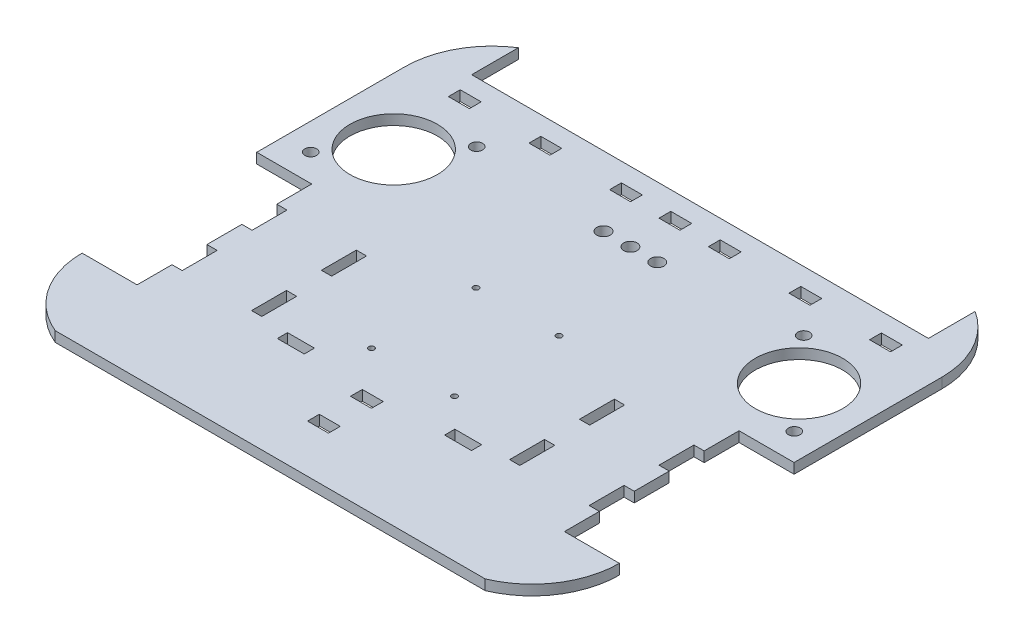
SolidWorks part; units mm, degrees
ref_plane "Front Plane" through (0, 0, 0) normal (0, 0, 1) x (1, 0, 0)
ref_plane "Top Plane" through (0, 0, 0) normal (0, 1, 0) x (1, 0, 0)
ref_plane "Right Plane" through (0, 0, 0) normal (1, 0, 0) x (0, 0, -1)
sketch "Sketch1" plane through (0, 0, 0) normal (0, 1, 0) x (1, 0, 0)
  line L1 (-127, 114.3) -> (127, 114.3)
  line L2 (-127, 114.3) -> (-127, -114.3)
  line L3 (-127, -114.3) -> (127, -114.3)
  line L4 (127, 114.3) -> (127, -114.3)
  line L5 (-127, 114.3) -> (127, -114.3) construction
  line L6 (-127, -114.3) -> (127, 114.3) construction
  point P0 (0, 0)
  dimension "D1" = 254
  dimension "D2" = 228.6
extrude "Boss-Extrude1" add sketch "Sketch1" along normal blind 4.826
sketch "Sketch2" plane through (0, 4.826, 0) normal (0, 1, 0) x (1, 0, 0)
  line L0 (-127, 114.3) -> (-127, -114.3) construction
  line L1 (-127, 6.35) -> (-101, 6.35)
  line L2 (-127, 6.35) -> (-127, -76.2)
  line L3 (-127, -76.2) -> (-101, -76.2)
  line L4 (-101, 6.35) -> (-101, -76.2)
  line L5 (127, -114.3) -> (127, 114.3) construction
  line L6 (127, 6.35) -> (101, 6.35)
  line L7 (127, 6.35) -> (127, -76.2)
  line L8 (127, -76.2) -> (101, -76.2)
  line L9 (101, 6.35) -> (101, -76.2)
  line L10 (-127, -114.3) -> (127, -114.3) construction
  dimension "D1" = 38.1
  dimension "D2" = 38.1
  dimension "D3" = 82.55
  dimension "D4" = 82.55
  dimension "D5" = 26
  dimension "D6" = 26
extrude "Cut-Extrude1" cut sketch "Sketch2" against normal blind 4.826
sketch "Sketch4" plane through (0, 4.826, 0) normal (0, 1, 0) x (1, 0, 0)
  line L0 (0, -114.3) -> (0, 114.3) construction
  line L1 (-127, -114.3) -> (127, -114.3) construction
  line L2 (127, 114.3) -> (-127, 114.3) construction
  line L3 (-127, 76.2) -> (-101.6, 76.2) construction
  line L4 (-127, 114.3) -> (-127, 6.35) construction
  line L5 (-101.6, 76.2) -> (-101.6, 114.3) construction
  line L6 (-127, 76.2) -> (-127, 114.3)
  line L7 (-127, 114.3) -> (-101.6, 114.3)
  line L8 (127, 76.2) -> (127, 114.3)
  line L9 (127, 114.3) -> (101.6, 114.3)
  arc A0 (-127, 76.2) -> (-101.6, 114.3) centre (-85.725, 76.2) cw
  arc A1 (127, 76.2) -> (101.6, 114.3) centre (85.725, 76.2) ccw
  dimension "D2" = 38.1
extrude "Cut-Extrude3" cut sketch "Sketch4" against normal blind 4.826
sketch "Sketch7" plane through (0, 4.826, 0) normal (0, 1, 0) x (1, 0, 0)
  line L0 (0, -114.3) -> (0, 114.3) construction
  line L1 (-127, -114.3) -> (127, -114.3) construction
  line L2 (101.6, 114.3) -> (-101.6, 114.3) construction
  line L3 (107.95, 88.9) -> (107.95, 114.3)
  line L4 (107.95, 88.9) -> (-107.95, 88.9)
  line L5 (0, 88.9) -> (0, 114.3)
  line L6 (107.95, 114.3) -> (-107.95, 114.3)
  line L7 (-107.95, 88.9) -> (-107.95, 114.3)
  line M6 (101.6, 114.3) -> (-101.6, 114.3)
  dimension "D2" = 107.95
extrude "Cut-Extrude5" cut sketch "Sketch7" against normal blind 4.826 contours L7 L4 L5 M6 | L5 L4 L3 M6 region at (53.975, 4.826, -101.6) region at (-53.975, 4.826, -101.6)
sketch "Sketch8" plane through (0, 4.826, 0) normal (0, 1, 0) x (1, 0, 0)
  line L0 (-127, -76.2) -> (-101.6, -76.2) construction
  line L1 (-101.6, -76.2) -> (-101.6, -114.3) construction
  line L2 (-127, -114.3) -> (127, -114.3) construction
  line L3 (-127, -76.2) -> (-127, -114.3)
  line L4 (-127, -114.3) -> (-101.6, -114.3)
  line L5 (0, -114.3) -> (0, 88.9) construction
  line L6 (107.95, 88.9) -> (-107.95, 88.9) construction
  line L7 (127, -114.3) -> (101.6, -114.3)
  line L8 (127, -76.2) -> (127, -114.3)
  arc A0 (-127, -76.2) -> (-101.6, -114.3) centre (-85.725, -76.2) ccw
  arc A1 (127, -76.2) -> (101.6, -114.3) centre (85.725, -76.2) cw
extrude "Cut-Extrude6" cut sketch "Sketch8" against normal blind 4.826
sketch "Sketch10" plane through (0, 4.826, 0) normal (0, 1, 0) x (1, 0, 0)
  line L0 (-101, -76.2) -> (-101, 6.35) construction
  line L1 (-101, -10.16) -> (-96.174, -10.16)
  line L2 (-101, -10.16) -> (-101, -26.67)
  line L3 (-101, -26.67) -> (-96.174, -26.67)
  line L4 (-96.174, -10.16) -> (-96.174, -26.67)
  line L5 (101, 6.35) -> (101, -76.2) construction
  line L6 (-101, -43.18) -> (-96.174, -43.18)
  line L7 (-101, -43.18) -> (-101, -59.69)
  line L8 (-101, -59.69) -> (-96.174, -59.69)
  line L9 (-96.174, -43.18) -> (-96.174, -59.69)
  line L10 (101, -10.16) -> (96.174, -10.16)
  line L11 (101, -10.16) -> (101, -26.67)
  line L12 (101, -26.67) -> (96.174, -26.67)
  line L13 (96.174, -10.16) -> (96.174, -26.67)
  line L14 (-101, 6.35) -> (-96.174, 6.35) construction
  line L15 (101, -43.18) -> (96.174, -43.18)
  line L16 (101, -43.18) -> (101, -59.69)
  line L17 (101, -59.69) -> (96.174, -59.69)
  line L18 (96.174, -43.18) -> (96.174, -59.69)
  line L19 (-96.174, 6.35) -> (-96.174, -10.16) construction
  line L20 (-96.174, -26.67) -> (-96.174, -43.18) construction
  line L21 (-96.174, -43.18) -> (-83.474, -80.9089) construction
  line L22 (-101, -76.2) -> (-96.174, -76.2)
  line L23 (-96.174, -76.2) -> (-96.174, -59.69)
  line L24 (-96.174, -59.69) -> (-83.474, -98.2941)
  line L25 (101, -76.2) -> (96.174, -76.2)
  line L26 (96.174, -76.2) -> (96.174, -59.69)
  line L27 (96.174, -43.18) -> (96.174, -26.67)
  line L28 (101, 6.35) -> (96.174, 6.35)
  line L29 (96.174, 6.35) -> (96.174, -10.16)
  line M19 (101, -76.2) -> (101, 6.35)
  line M35 (-101, 6.35) -> (-101, -76.2)
  dimension "D1" = 4.826
  dimension "D2" = 4.826
extrude "Cut-Extrude8" cut sketch "Sketch10" against normal through all contours L9 L6 L8 M35 | L10 L13 L12 M19 | L15 L18 L17 M19 | L2 L3 L4 L1 region at (-98.587, 4.826, 51.435) region at (98.587, 4.826, 18.415) region at (98.587, 4.826, 51.435)
sketch "Sketch12" plane through (0, 0, 0) normal (0, -1, 0) x (1, 0, 0)
  line L0 (-58.582, 43.18) -> (-58.582, 59.69) construction
  line L1 (-58.582, 43.18) -> (-63.408, 43.18) construction
  line L2 (-63.408, 43.18) -> (-63.408, 59.69) construction
  line L3 (-58.582, 59.69) -> (-63.408, 59.69) construction
  line L4 (-58.582, 26.67) -> (-63.408, 26.67) construction
  line L5 (-58.582, 10.16) -> (-58.582, 26.67) construction
  line L6 (-58.582, 10.16) -> (-63.408, 10.16) construction
  line L7 (-63.408, 10.16) -> (-63.408, 26.67) construction
  line L8 (-58.582, 43.18) -> (-58.582, 59.69)
  line L9 (-58.582, 43.18) -> (-63.408, 43.18)
  line L10 (-63.408, 43.18) -> (-63.408, 59.69)
  line L11 (-58.582, 59.69) -> (-63.408, 59.69)
  line L12 (-58.582, 26.67) -> (-63.408, 26.67)
  line L13 (-58.582, 10.16) -> (-58.582, 26.67)
  line L14 (-58.582, 10.16) -> (-63.408, 10.16)
  line L15 (-63.408, 10.16) -> (-63.408, 26.67)
extrude "Cut-Extrude9" cut sketch "Sketch12" against normal through all
sketch "Sketch13" plane through (0, 4.826, 0) normal (0, 1, 0) x (1, 0, 0)
  line L0 (63.408, -43.18) -> (63.408, -59.69) construction
  line L1 (63.408, -43.18) -> (58.582, -43.18) construction
  line L2 (58.582, -43.18) -> (58.582, -59.69) construction
  line L3 (63.408, -59.69) -> (58.582, -59.69) construction
  line L4 (63.408, -26.67) -> (58.582, -26.67) construction
  line L5 (63.408, -10.16) -> (63.408, -26.67) construction
  line L6 (63.408, -10.16) -> (58.582, -10.16) construction
  line L7 (58.582, -10.16) -> (58.582, -26.67) construction
  line L8 (63.408, -43.18) -> (63.408, -59.69)
  line L9 (63.408, -43.18) -> (58.582, -43.18)
  line L10 (58.582, -43.18) -> (58.582, -59.69)
  line L11 (63.408, -59.69) -> (58.582, -59.69)
  line L12 (63.408, -26.67) -> (58.582, -26.67)
  line L13 (63.408, -10.16) -> (63.408, -26.67)
  line L14 (63.408, -10.16) -> (58.582, -10.16)
  line L15 (58.582, -10.16) -> (58.582, -26.67)
extrude "Cut-Extrude10" cut sketch "Sketch13" against normal through all
sketch "Sketch14" plane through (0, 4.826, 0) normal (0, 1, 0) x (1, 0, 0)
  line L0 (-127, 6.35) -> (127, 6.35) construction
  line L1 (0, 6.35) -> (0, -114.3) construction
  line L2 (-101.6, -114.3) -> (101.6, -114.3) construction
  line L3 (-22.86, 6.35) -> (-22.86, -114.3) construction
  line L4 (22.86, 6.35) -> (22.86, -114.3) construction
  dimension "D1" = 22.86
sketch "Sketch15" plane through (0, 4.826, 0) normal (0, 1, 0) x (1, 0, 0)
  circle A0 centre (19.5961, 2.6692) radius 1.3462 construction
  circle A1 centre (-19.6723, 2.6692) radius 1.3462 construction
  circle A2 centre (-19.6723, -46.7636) radius 1.3462 construction
  circle A3 centre (19.5961, -46.7636) radius 1.3462 construction
  circle A4 centre (19.5961, 2.6692) radius 1.3462
  circle A5 centre (-19.6723, 2.6692) radius 1.3462
  circle A6 centre (-19.6723, -46.7636) radius 1.3462
  circle A7 centre (19.5961, -46.7636) radius 1.3462
extrude "Cut-Extrude11" cut sketch "Sketch15" against normal through all
sketch "Sketch16" plane through (0, 4.826, 0) normal (0, 1, 0) x (1, 0, 0)
  line L0 (0, 88.9) -> (0, -114.3) construction
  line L1 (107.95, 88.9) -> (-107.95, 88.9) construction
  circle A0 centre (77.2939, 60.6102) radius 2.7781 construction
  circle A1 centre (114.3, 19.1646) radius 2.7781 construction
  circle A2 centre (95.7969, 39.8874) radius 20.6375 construction
  circle A3 centre (77.2939, 60.6102) radius 2.7781
  circle A4 centre (114.3, 19.1646) radius 2.7781
  circle A5 centre (95.7969, 39.8874) radius 20.6375
  circle A6 centre (-95.7969, 39.8874) radius 20.6375
  circle A7 centre (-77.2939, 60.6102) radius 2.7781
  circle A8 centre (-114.3, 19.1646) radius 2.7781
extrude "Cut-Extrude12" cut sketch "Sketch16" against normal through all
sketch "Sketch17" plane through (0, 4.826, 0) normal (0, 1, 0) x (1, 0, 0)
  line L0 (-56.4929, 80.0388) -> (-56.4929, 74.4508)
  line L1 (-104.4989, 80.0388) -> (-94.5929, 80.0388)
  line L2 (-104.4989, 80.0388) -> (-104.4989, 74.4508)
  line L3 (-104.4989, 74.4508) -> (-94.5929, 74.4508)
  line L4 (-94.5929, 80.0388) -> (-94.5929, 74.4508)
  line L9 (-66.3989, 80.0388) -> (-56.4929, 80.0388)
  line L10 (-66.3989, 80.0388) -> (-66.3989, 74.4508)
  line L11 (-66.3989, 74.4508) -> (-56.4929, 74.4508)
  line L12 (-18.3929, 80.0388) -> (-18.3929, 74.4508)
  line L13 (-28.2989, 80.0388) -> (-18.3929, 80.0388)
  line L14 (-28.2989, 80.0388) -> (-28.2989, 74.4508)
  line L15 (-28.2989, 74.4508) -> (-18.3929, 74.4508)
  line L16 (-127, 76.2) -> (-127, 6.35) construction
  line L17 (0, 88.9) -> (0, -114.3)
  line L18 (107.95, 88.9) -> (-107.95, 88.9) construction
  line L19 (-94.5929, 74.4508) -> (-78.3377, 74.4508) construction
  line L20 (18.3929, 80.0388) -> (18.3929, 74.4508)
  line L21 (28.2989, 80.0388) -> (18.3929, 80.0388)
  line L22 (28.2989, 80.0388) -> (28.2989, 74.4508)
  line L23 (28.2989, 74.4508) -> (18.3929, 74.4508)
  line L24 (56.4929, 80.0388) -> (56.4929, 74.4508)
  line L25 (66.3989, 74.4508) -> (56.4929, 74.4508)
  line L26 (66.3989, 80.0388) -> (66.3989, 74.4508)
  line L27 (66.3989, 80.0388) -> (56.4929, 80.0388)
  line L28 (104.4989, 80.0388) -> (94.5929, 80.0388)
  line L29 (104.4989, 80.0388) -> (104.4989, 74.4508)
  line L30 (104.4989, 74.4508) -> (94.5929, 74.4508)
  line L31 (94.5929, 80.0388) -> (94.5929, 74.4508)
  line L36 (4.953, 74.4508) -> (4.953, 80.0388)
  line L37 (4.953, 74.4508) -> (-4.953, 74.4508)
  line L38 (4.953, 80.0388) -> (-4.953, 80.0388)
  line L39 (-4.953, 74.4508) -> (-4.953, 80.0388)
  line L40 (4.953, 74.4508) -> (-4.953, 80.0388) construction
  line L41 (4.953, 80.0388) -> (-4.953, 74.4508) construction
  point P42 (0, 77.2448)
  dimension "D1" = 9.906
  dimension "D2" = 5.588
  dimension "D6" = 3
  dimension "D7" = 22.5011
  dimension "D8" = 9.906
  dimension "D9" = 0
extrude "Cut-Extrude13" cut sketch "Sketch17" against normal through all contours L28 L31 L30 L29 | L26 L27 L24 L25 | L23 L22 L21 L20 | L36 L38 L17 L37 | L39 L37 L17 L38 | L14 L15 L12 L13 | L10 L11 L0 L9 | L4 L1 L2 L3 region at (-61.4459, 4.826, -77.2448) region at (-99.5459, 4.826, -77.2448) region at (-23.3459, 4.826, -77.2448) region at (2.4765, 4.826, -77.2448) region at (-2.4765, 4.826, -77.2448) region at (23.3459, 4.826, -77.2448) region at (61.4459, 4.826, -77.2448) region at (99.5459, 4.826, -77.2448)
sketch "Sketch18" plane through (0, 4.826, 0) normal (0, 1, 0) x (1, 0, 0)
  line L0 (-4.953, -91.694) -> (4.953, -91.694)
  line L1 (-4.953, -91.694) -> (-4.953, -86.106)
  line L2 (4.953, -91.694) -> (4.953, -86.106)
  line L3 (-4.953, -86.106) -> (4.953, -86.106)
  line L4 (-4.953, -91.694) -> (4.953, -86.106) construction
  line L5 (4.953, -91.694) -> (-4.953, -86.106) construction
  line L6 (0, 6.35) -> (0, -114.3) construction
  line L7 (-4.953, -71.374) -> (4.953, -71.374)
  line L8 (-4.953, -71.374) -> (-4.953, -65.786)
  line L9 (4.953, -71.374) -> (4.953, -65.786)
  line L10 (-4.953, -65.786) -> (4.953, -65.786)
  line L11 (-4.953, -71.374) -> (4.953, -65.786) construction
  line L12 (4.953, -71.374) -> (-4.953, -65.786) construction
  point P1 (0, -88.9)
  point P10 (0, -68.58)
  dimension "D1" = 9.906
  dimension "D2" = 5.588
  dimension "D3" = 0
  dimension "D4" = 25.4
  dimension "D5" = 2
extrude "Cut-Extrude14" cut sketch "Sketch18" against normal through all
sketch "Sketch19" plane through (0, 4.826, 0) normal (0, 1, 0) x (1, 0, 0)
  circle A0 centre (0, 55.982) radius 3.175
  circle A1 centre (12.7, 55.982) radius 3.175
  circle A2 centre (-12.7, 55.982) radius 3.175
  dimension "D1" = 6.35
  dimension "D2" = 2
  dimension "D3" = 2
extrude "Cut-Extrude15" cut sketch "Sketch19" against normal through all
sketch "Sketch22" plane through (0, 0, 0) normal (0, -1, 0) x (1, 0, 0)
  line L0 (-33.182, 60.198) -> (-45.882, 60.198) construction
  line L1 (-33.182, 60.198) -> (-33.182, 65.024) construction
  line L2 (-33.182, 65.024) -> (-45.882, 65.024) construction
  line L3 (-45.882, 60.198) -> (-45.882, 65.024) construction
  line L4 (33.182, 60.198) -> (45.882, 60.198) construction
  line L5 (45.882, 65.024) -> (45.882, 60.198) construction
  line L6 (33.182, 65.024) -> (45.882, 65.024) construction
  line L7 (33.182, 65.024) -> (33.182, 60.198) construction
  line L8 (-33.182, 60.198) -> (-45.882, 60.198)
  line L9 (-33.182, 60.198) -> (-33.182, 65.024)
  line L10 (-33.182, 65.024) -> (-45.882, 65.024)
  line L11 (-45.882, 60.198) -> (-45.882, 65.024)
  line L12 (33.182, 60.198) -> (45.882, 60.198)
  line L13 (45.882, 65.024) -> (45.882, 60.198)
  line L14 (33.182, 65.024) -> (45.882, 65.024)
  line L15 (33.182, 65.024) -> (33.182, 60.198)
extrude "Cut-Extrude18" cut sketch "Sketch22" against normal through all
equation "\"MDF\"= 0.19in"
equation "\"GenDiameter\"= 60mm"
equation "\"GenCutDiameter\" = 1.8in"
equation "\"GenCutDistance\" = 1"
equation "\"TowerHeight\" = 6in"
equation "\"TowerFrontBase\" = 3in"
equation "\"FunnelHeight\" = 1in"
equation "\"FunnelAngle\" = 20"
equation "\"TowerSideBase\" = 3in"
equation "\"BaseLength\" = 9in"
equation "\"BaseWidth\" = 10in"
equation "\"WheelHoleLength\" = 3.25in"
equation "\"WheelHoleWidth\" = 26mm"
equation "\"DropLength\" = 1in"
equation "\"D1@Sketch1\"=\"BaseWidth\""
equation "\"D2@Sketch1\"=\"BaseLength\""
equation "\"D1@Boss-Extrude1\"=\"MDF\""
equation "\"WheelHoleFromBack\" = 1.5in"
equation "\"D1@Sketch2\"=\"WheelHoleFromBack\""
equation "\"D2@Sketch2\"=\"WheelHoleFromBack\""
equation "\"D3@Sketch2\"=\"WheelHoleLength\""
equation "\"D4@Sketch2\"=\"WheelHoleLength\""
equation "\"D5@Sketch2\"=\"WheelHoleWidth\""
equation "\"D6@Sketch2\"=\"WheelHoleWidth\""
equation "\"D1@Cut-Extrude1\"=\"MDF\""
equation "\"DropWidth\" = 8.5in"
equation "\"BumperWidth\" = 1in"
equation "\"D1@Sketch4\"=\"BumperWidth\""
equation "\"D2@Sketch4\"=\"WheelHoleFromBack\""
equation "\"D1@Cut-Extrude3\"=\"MDF\""
equation "\"D1@Sketch7\"=\"DropLength\""
equation "\"D2@Sketch7\"=\"DropWidth\"/2"
equation "\"D1@Cut-Extrude5\"=\"MDF\""
equation "\"D1@Sketch8\"=\"BumperWidth\""
equation "\"D1@Cut-Extrude6\"=\"MDF\""
equation "\"D1@Sketch10\"=\"MDF\""
equation "\"D2@Sketch10\"=\"MDF\""
